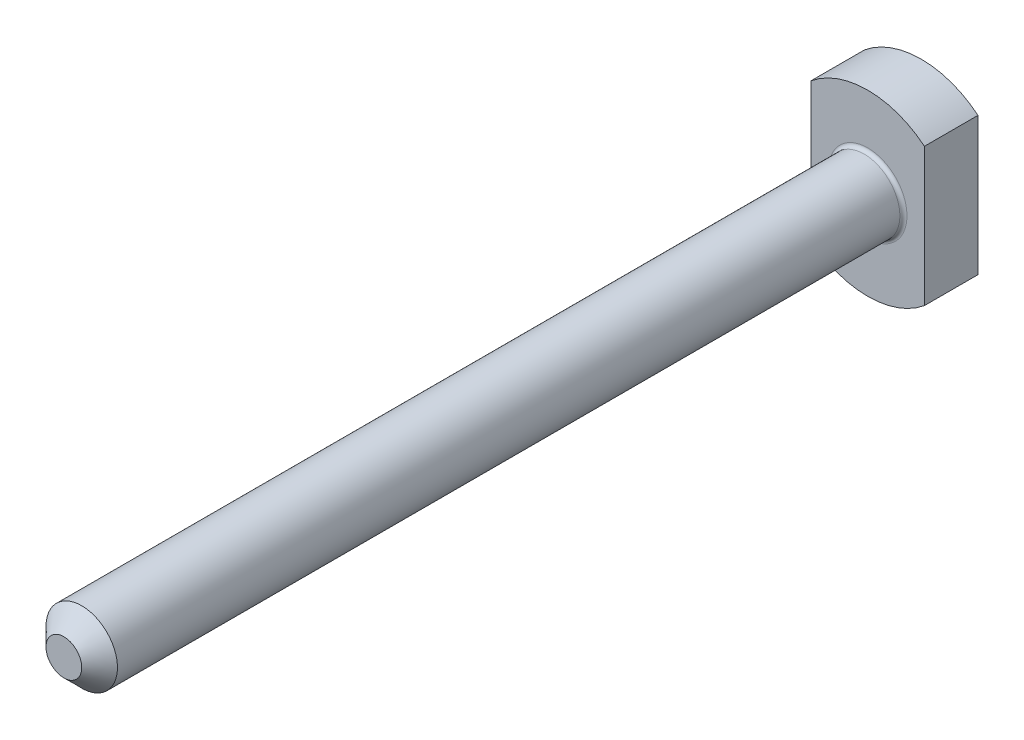
SolidWorks part; units mm, degrees
ref_plane "Front Plane" through (0, 0, 0) normal (0, 0, 1) x (1, 0, 0)
ref_plane "Top Plane" through (0, 0, 0) normal (0, 1, 0) x (1, 0, 0)
ref_plane "Right Plane" through (0, 0, 0) normal (1, 0, 0) x (0, 0, -1)
sketch "Sketch1" plane through (0, 0, 0) normal (0, 0, 1) x (1, 0, 0)
  circle A0 centre (0, 0) radius 2
  dimension "D1" = 4
extrude "Boss-Extrude1" add sketch "Sketch1" along normal blind 45
sketch "Sketch2" plane through (0, 0, 0) normal (0, 0, -1) x (-1, 0, 0)
  line L0 (-3.175, 3.8626) -> (-3.175, -3.8626)
  line L1 (3.175, 3.8626) -> (3.175, -3.8626)
  arc A0 (-3.175, -3.8626) -> (3.175, -3.8626) centre (0, 0) ccw
  arc A1 (3.175, 3.8626) -> (-3.175, 3.8626) centre (0, 0) ccw
  dimension "D1" = 10
  dimension "D2" = 6.35
extrude "Boss-Extrude2" add sketch "Sketch2" along normal blind 3
chamfer "Chamfer1" distance 1 angle 45 1 edges at (2, 0, 45)
fillet "Fillet1" radius 0.2 1 edges at (2, 0, 0)
